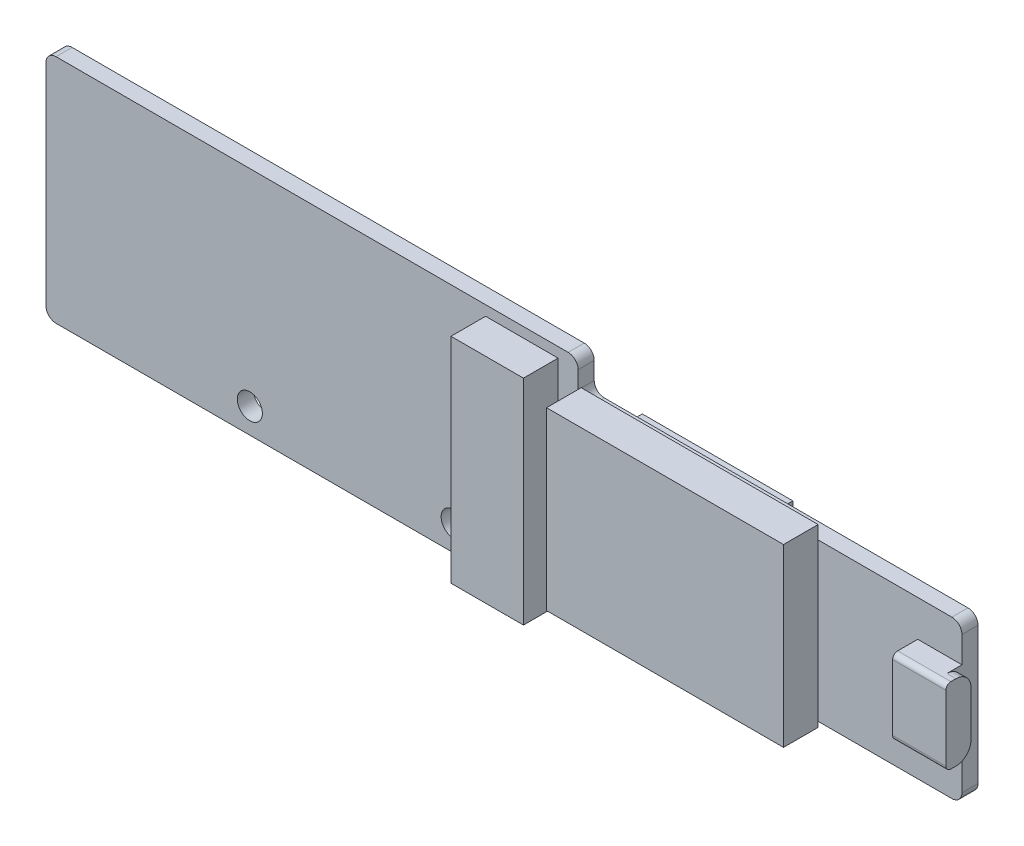
SolidWorks part; units mm, degrees
ref_plane "Front Plane" through (0, 0, 0) normal (0, 0, 1) x (1, 0, 0)
ref_plane "Top Plane" through (0, 0, 0) normal (0, 1, 0) x (1, 0, 0)
ref_plane "Right Plane" through (0, 0, 0) normal (1, 0, 0) x (0, 0, -1)
sketch "Sketch1" plane through (0, 0, 0) normal (0, 0, 1) x (1, 0, 0)
  line L0 (53, 19.27) -> (63.0723, 19.27) construction
  line L1 (0, 0) -> (53, 0)
  line L2 (0, 0) -> (0, 23)
  line L3 (0, 23) -> (53, 23)
  line L4 (53, 0) -> (53, 3.62)
  line L5 (47.5491, 11.445) -> (74.8048, 11.445) construction
  line L6 (53, 3.62) -> (63.0723, 3.62) construction
  line L7 (53, 19.27) -> (53, 23)
  line L8 (53, 19.27) -> (91.22, 19.27)
  line L10 (53, 3.62) -> (91.22, 3.62)
  line L11 (91.22, 19.27) -> (91.22, 3.62)
  circle A0 centre (40.6, 2.5) radius 1.25
  circle A1 centre (20.3, 2.5) radius 1.25
  dimension "D8" = 2.5
  dimension "D9" = 12.4
  dimension "D10" = 20.3
  dimension "D11" = 2.5
  dimension "D1" = 3.73
  dimension "D2" = 91.22
  dimension "D3" = 53
  dimension "D4" = 23
  dimension "D5" = 15.65
  dimension "D6" = 3.62
  dimension "D7" = 19.38
extrude "Boss-Extrude2" add sketch "Sketch1" along normal blind 1.6
sketch "Sketch2" plane through (0, 0, 0) normal (0, 0, -1) x (-1, 0, 0)
  line L0 (-91.22, 3.62) -> (-91.22, 19.27) construction
  line L1 (-72.12, 19.12) -> (-57.12, 19.12)
  line L2 (-72.12, 19.12) -> (-72.12, 3.77)
  line L3 (-72.12, 3.77) -> (-57.12, 3.77)
  line L4 (-57.12, 19.12) -> (-57.12, 3.77)
  line L5 (-72.12, 19.12) -> (-57.12, 3.77) construction
  line L6 (-72.12, 3.77) -> (-57.12, 19.12) construction
  line L7 (-91.22, 19.27) -> (-53, 19.27) construction
  line L8 (-53, 3.62) -> (-91.22, 3.62) construction
  point P0 (-64.62, 11.445)
  dimension "D1" = 34.1
  dimension "D2" = 15.5
  dimension "D3" = 0.15
  dimension "D4" = 0.15
extrude "Boss-Extrude3" add sketch "Sketch2" along normal blind 0.66
sketch "Sketch3" plane through (0, 0, 1.6) normal (0, 0, 1) x (1, 0, 0)
  line L1 (86.82, 15.66) -> (92.12, 15.66)
  line L2 (86.82, 15.66) -> (86.82, 8.12)
  line L3 (86.82, 8.12) -> (92.12, 8.12)
  line L4 (92.12, 15.66) -> (92.12, 8.12)
  line L5 (86.82, 15.66) -> (92.12, 8.12) construction
  line L6 (86.82, 8.12) -> (92.12, 15.66) construction
  line L7 (91.22, 19.27) -> (53, 19.27) construction
  line L9 (91.22, 3.62) -> (91.22, 19.27) construction
  point P0 (89.47, 11.89)
  dimension "D1" = 7.54
  dimension "D2" = 5.3
  dimension "D3" = 11.15
  dimension "D4" = 0.9
extrude "Boss-Extrude4" add sketch "Sketch3" along normal blind 2.5
fillet "Fillet1" radius 0.5 2 edges at (89.47, 8.12, 4.1) (89.47, 15.66, 4.1)
fillet "Fillet2" radius 1.5 2 edges at (91.67, 8.12, 1.6) (91.67, 15.66, 1.6)
sketch "Sketch4" plane through (0, 0, 0) normal (0, 0, -1) x (-1, 0, 0)
  line L0 (-4.4, 15.24) -> (0.9, 15.24)
  line L1 (-4.4, 15.24) -> (-4.4, 7.7)
  line L2 (-4.4, 7.7) -> (0.9, 7.7)
  line L3 (0.9, 15.24) -> (0.9, 7.7)
  line L4 (-4.4, 15.24) -> (0.9, 7.7) construction
  line L5 (-4.4, 7.7) -> (0.9, 15.24) construction
  line L6 (-53, 23) -> (0, 23) construction
  line L7 (0, 23) -> (0, 0) construction
  point P0 (-1.75, 11.47)
  dimension "D1" = 15.3
  dimension "D2" = 5.3
  dimension "D3" = 7.54
  dimension "D4" = 0.9
extrude "Boss-Extrude5" add sketch "Sketch4" along normal blind 2.5
fillet "Fillet3" radius 0.5 2 edges at (1.75, 7.7, -2.5) (1.75, 15.24, -2.5)
fillet "Fillet4" radius 1.5 2 edges at (-0.45, 7.7, 0) (-0.45, 15.24, 0)
sketch "Sketch5" plane through (0, 0, 1.6) normal (0, 0, 1) x (1, 0, 0)
  line L0 (53, 23) -> (0, 23) construction
  line L1 (43.78, 22) -> (51, 22)
  line L2 (43.78, 22) -> (43.78, 0.7)
  line L3 (43.78, 0.7) -> (51, 0.7)
  line L4 (51, 22) -> (51, 0.7)
  line L5 (43.78, 22) -> (51, 0.7) construction
  line L6 (43.78, 0.7) -> (51, 22) construction
  line L7 (53.3, 20.6) -> (76.9, 20.6)
  line L8 (53.3, 20.6) -> (53.3, 3.1)
  line L9 (53.3, 3.1) -> (76.9, 3.1)
  line L10 (76.9, 20.6) -> (76.9, 3.1)
  line L11 (53.3, 20.6) -> (76.9, 3.1) construction
  line L12 (53.3, 3.1) -> (76.9, 20.6) construction
  line L13 (53, 0) -> (53, 3.62) construction
  point P0 (47.39, 11.35)
  point P5 (65.1, 11.85)
  dimension "D1" = 7.22
  dimension "D2" = 21.3
  dimension "D3" = 22.3
  dimension "D4" = 2
  dimension "D5" = 2.3
  dimension "D6" = 23.6
  dimension "D7" = 17.5
  dimension "D8" = 2.4
extrude "Boss-Extrude6" add sketch "Sketch5" along normal blind 3.45
fillet "Fillet5" radius 1 8 edges at (91.22, 3.62, 0.8) (91.22, 19.27, 0.8) (0, 23, 0.8) (0, 0, 0.8) (53, 0, 0.8) (53, 23, 0.8) (53, 19.27, 0.8) (53, 3.62, 0.8)
